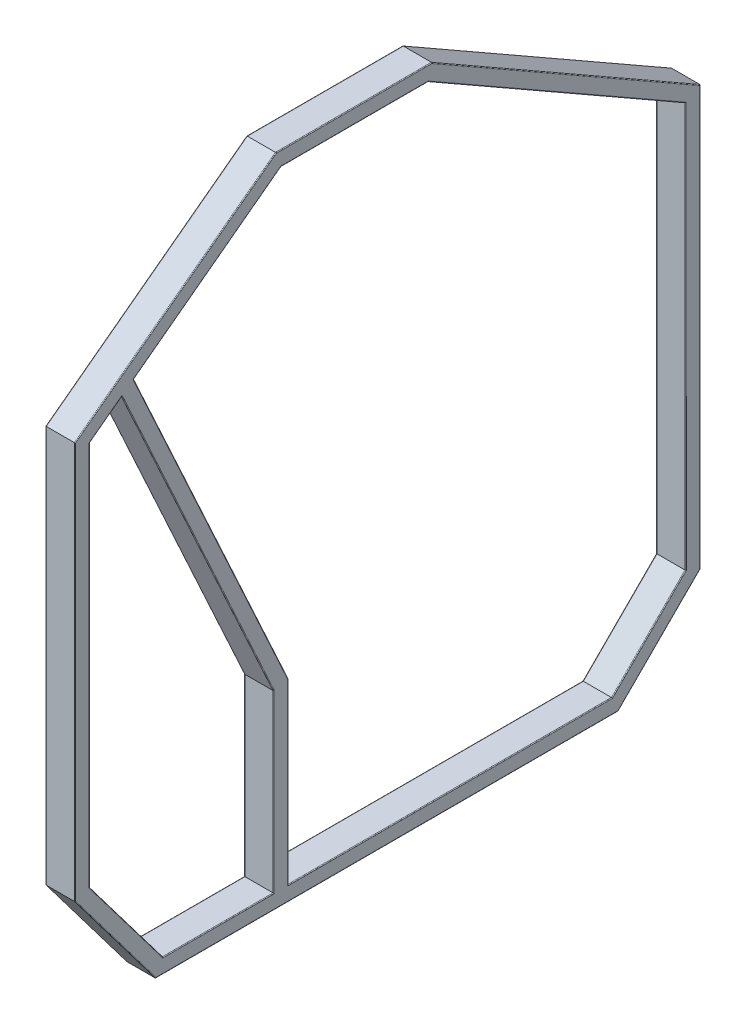
SolidWorks part; units mm, degrees
ref_plane "Plan de face" through (0, 0, 0) normal (0, 0, 1) x (1, 0, 0)
ref_plane "Plan de dessus" through (0, 0, 0) normal (0, 1, 0) x (1, 0, 0)
ref_plane "Plan de droite" through (0, 0, 0) normal (1, 0, 0) x (0, 0, -1)
sketch "Esquisse1" plane through (0, 0, 0) normal (1, 0, 0) x (0, 0, -1)
  line L0 (0, 0) -> (-400, 0)
  line L1 (-400, 0) -> (-800, 528.5714) construction
  line L2 (-800, 1400) -> (-800, 528.5714) construction
  line L3 (-400, 1700) -> (-800, 1400)
  line L4 (-400, 1700) -> (0, 1700)
  line L5 (0, 1700) -> (700, 1300)
  line L6 (700, 1300) -> (700, 200)
  line L7 (0, 0) -> (500, 0)
  line L8 (0, 0) -> (0, 1700) construction
  line L9 (500, 0) -> (700, 200)
  line L10 (-400, 1700) -> (-400, 0) construction
  line L11 (500, 0) -> (500, 200) construction
  line L12 (500, 200) -> (700, 200) construction
  line L13 (700, 1300) -> (0, 1300) construction
  line L14 (-800, 528.5714) -> (-400, 528.5714) construction
  line L15 (-400, 1700) -> (-400, 1400) construction
  line L16 (-400, 1400) -> (-800, 1400) construction
  line L17 (740, 1323.2129) -> (740, 183.4315)
  line L18 (516.5685, -40) -> (740, 183.4315)
  line L19 (0, -40) -> (516.5685, -40)
  line L20 (0, -40) -> (-419.8924, -40)
  line L21 (-419.8924, -40) -> (-840, 515.1422) construction
  line L22 (-840, 1420) -> (-840, 515.1422) construction
  line L23 (-413.3333, 1740) -> (-840, 1420)
  line L24 (-413.3333, 1740) -> (10.6226, 1740)
  line L25 (10.6226, 1740) -> (740, 1323.2129)
  line L26 (-800, 1400) -> (-400, 528.5714)
  line L27 (-400, 528.5714) -> (-380, 485)
  line L28 (-380, 485) -> (-380, 0)
  line L29 (-420, 26.4286) -> (-420, 476.2581)
  line L30 (-800, 1304.1153) -> (-420, 476.2581)
  line L31 (-419.8924, -40) -> (-740.5405, -40)
  line L32 (-740.5405, -40) -> (-960, 250)
  line L33 (-960, 250) -> (-960, 1330)
  line L34 (-960, 1330) -> (-840, 1420)
  line L35 (-832.7411, 1375.4442) -> (-920, 1310)
  line L36 (-920, 1310) -> (-920, 263.4292)
  line L37 (-920, 263.4292) -> (-720.6482, 0)
  line L38 (-720.6482, 0) -> (-450.1626, 0)
  line L39 (-420, 26.4286) -> (-420, 0)
  line L40 (-554.5716, 0) -> (-420, 0)
  line L41 (-832.7411, 1375.4442) -> (-800, 1304.1153)
  line L42 (-800, 1400) -> (-832.7411, 1375.4442) construction
  dimension "D1" = 400
  dimension "D2" = 0
  dimension "D3" = 700
  dimension "D4" = 200
  dimension "D5" = 200
  dimension "D6" = 1700
  dimension "D7" = 1300
  dimension "D8" = 915
  dimension "D9" = 400
  dimension "D10" = 300
  dimension "D12" = 20
  dimension "D13" = 40
  dimension "D14" = 40
  dimension "D15" = 40
  dimension "D16" = 40
  dimension "D17" = 40
  dimension "D18" = 40
  dimension "D19" = 500
  dimension "D20" = 250
  dimension "D11" = 40
extrude "Boss.-Extru.1" add sketch "Esquisse1" along normal blind 80
shell "Coque1" thickness 4
fillet "Congé2" radius 2 88 edges at (80, 942.5, 590) (80, 1550, 600) (80, 1700, 200) (0, 786.7146, 920) (0, 131.7146, 820.3241) (80, 1500, -350) (0, 0, 570.3241) (0, 238.1291, 420) (0, 925.8512, 626.3706) (0, 1342.7221, 876.3706) (0, 1740, 201.3554) (0, 1531.6065, -375.3113) (0, 753.3222, -740) (80, 750, -700) (0, 71.7157, -628.2843) (0, -40, 111.986) (0, 105, 850.2703) (0, 790, 960) (0, 1535, 686.6667) (0, 0, -60) (0, 100, -600) (80, 100, -600) (0, 750, -700) (0, 1500, -350) (0, 1700, 200) (0, 1550, 600) (0, 942.5, 590) (0, 242.5, 380) (80, 0, -60) (80, 1535, 686.6667) (80, 790, 960) (80, 105, 850.2703) (80, -40, 111.986) (80, 71.7157, -628.2843) (80, 753.3222, -740) (80, 1531.6065, -375.3113) (80, 242.5, 380) (76, 1346.8096, 877.5872) (4, 929.3758, 623.5872) (76, 236.5662, 416) (76, -4, 569.3187) (80, 1740, 201.3554) (76, 129.0431, 823.3187) (76, 1532, 684) (76, 789.6715, 956) (76, 107.6715, 847.2757) (76, -36, 111.8198) (4, 74.5442, -625.4558) (76, 752.99, -736) (76, 1528.4458, -372.7802) (76, 240.0629, 384) (76, 942.6949, 594.4907) (76, 1552.632, 603.1574) (4, 1704, 200.1355) (4, 1503.1606, -352.5311) (4, 750.3322, -704) (76, 97.1716, -602.8284) (76, 1736, 201.2198) (76, -4, -58.8284) (76, 787.0431, 924) (76, 1704, 200.1355) (76, 1503.1606, -352.5311) (76, 750.3322, -704) (76, 74.5442, -625.4558) (80, 1342.7221, 876.3706) (76, 929.3758, 623.5872) (4, 240.0629, 384) (4, -4, -58.8284) (4, 97.1716, -602.8284) (4, 1552.632, 603.1574) (4, 942.6949, 594.4907) (4, 1532, 684) (4, 1736, 201.2198) (4, 1528.4458, -372.7802) (4, 752.99, -736) (4, -36, 111.8198) (4, 107.6715, 847.2757) (4, 789.6715, 956) (4, 1346.8096, 877.5872) (4, 787.0431, 924) (4, 129.0431, 823.3187) (4, -4, 569.3187) (4, 236.5662, 416) (80, 925.8512, 626.3706) (80, 238.1291, 420) (80, 0, 570.3241) (80, 131.7146, 820.3241) (80, 786.7146, 920)
